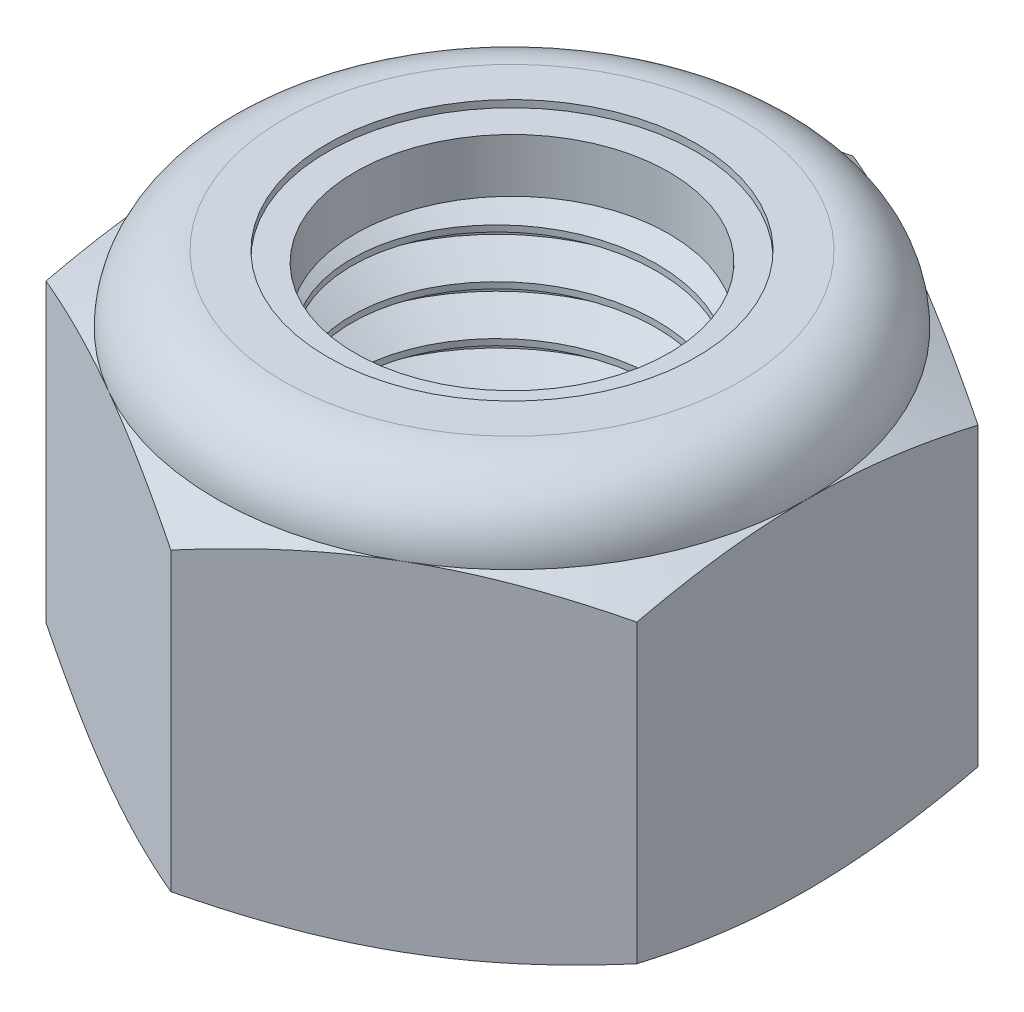
SolidWorks part; units mm, degrees
note: '?' marks a value the reader was unsure of.
ref_plane "Front" through (0, 0, 0) normal (0, 0, 1) x (1, 0, 0)
ref_plane "Top" through (0, 0, 0) normal (0, 1, 0) x (1, 0, 0)
ref_plane "Right" through (0, 0, 0) normal (1, 0, 0) x (0, 0, -1)
sketch "Sketch8" plane through (0, 0, 0) normal (1, 0, 0) x (0, 0, -1)
  line L0 (0, 0) -> (0, 8.7312) construction
  line L1 (6.35, 0) -> (-6.35, 0) construction
  line L2 (-3.9688, 8.7312) -> (3.9688, 8.7312) construction
  line L3 (3.9688, 8.7312) -> (3.9688, 7.6729) construction
sketch "Sketch1" plane through (0, 0, 0) normal (0, 1, 0) x (1, 0, 0)
  line L1 (0, 7.3323) -> (-6.35, 3.6662)
  line L2 (-6.35, 3.6662) -> (-6.35, -3.6662)
  line L3 (-6.35, -3.6662) -> (0, -7.3323)
  line L4 (0, -7.3323) -> (6.35, -3.6662)
  line L5 (6.35, -3.6662) -> (6.35, 3.6662)
  line L6 (6.35, 3.6662) -> (0, 7.3323)
  circle A0 centre (0, 0) radius 6.35 construction
  circle A1 centre (0, 0) radius 3.9688
extrude "Extrude1" add sketch "Sketch1" along normal up to vertex (8.7312 mm away) up to point (0, 8.7312, 0)
sketch "Sketch5" plane through (0, 0, 0) normal (1, 0, 0) x (0, 0, -1)
  line L0 (0, 0) -> (6.35, 0)
  line L1 (6.35, 0) -> (7.3323, 0.4581)
  line L2 (7.3323, 0.4581) -> (7.3323, 6.818)
  line L3 (7.3323, 6.818) -> (6.35, 7.276)
  line L4 (4.8948, 8.7312) -> (4.8948, 10.0012)
  line L5 (4.8948, 10.0012) -> (8.6023, 10.0012)
  line L6 (8.6023, 10.0012) -> (8.6023, -1.27)
  line L7 (8.6023, -1.27) -> (0, -1.27)
  line L8 (0, -1.27) -> (0, 0)
  line L9 (6.35, 7.276) -> (6.35, 0) construction
  line L12 (7.3323, 8.7312) -> (7.3323, 0) construction
  line L13 (7.3323, 4.3656) -> (8.6023, 4.3656) construction
  line L15 (0, 0) -> (0, 10.0012) construction
  line L18 (6.35, 0) -> (-6.35, 0) construction
  line L19 (3.6662, 8.7312) -> (7.3323, 8.7312) construction
  line L20 (0, 10.0012) -> (4.8948, 10.0012) construction
  line L21 (3.6662, 0) -> (7.3323, 0) construction
  arc A0 (6.35, 7.276) -> (4.8948, 8.7312) centre (4.8948, 7.276) ccw
  dimension "D1" = 25
  dimension "D2" = 1.27
  dimension "D4" = 1.4552
revolve "Cut-Revolve3" cut sketch "Sketch5" angle 360 about L15
sketch "Sketch4" plane through (0, 0, 0) normal (1, 0, 0) x (0, 0, -1)
  line L0 (0, 7.276) -> (4.3656, 7.276)
  line L1 (4.3656, 7.276) -> (0, 5.2403)
  line L3 (0, 2.0357) -> (4.3656, 0)
  line L4 (4.3656, 0) -> (0, 0)
  line L5 (0, 0) -> (0, 7.276) construction
  line L10 (0, 0) -> (0, 8.7312) construction
  line L11 (0, 2.0357) -> (0, 0)
  line L12 (0, 7.276) -> (0, 5.2403)
  line L13 (5.4993, 7.276) -> (0, 7.276) construction
  dimension "D1" = 25
  dimension "D2" = 8.7312
sketch "Sketch6" plane through (0, 0, 0) normal (1, 0, 0) x (0, 0, -1)
  line L0 (0, 7.276) -> (6.1976, 7.276)
  line L1 (4.8948, 8.5788) -> (2.4474, 8.5788)
  line L2 (0, 10.0012) -> (0, 7.276)
  line L3 (2.4474, 10.0012) -> (0, 10.0012)
  line L4 (0, 10.0012) -> (4.8948, 10.0012) construction
  line L5 (0, 0) -> (0, 10.0012) construction
  line L6 (0, 10.0012) -> (0, 0) construction
  line L7 (2.4474, 8.5788) -> (2.4474, 10.0012)
  line L8 (4.8948, 8.7312) -> (4.8948, 8.5788) construction
  line L9 (2.4474, 8.5788) -> (0, 8.5788) construction
  line L10 (0, 8.5788) -> (0, 5.2403) construction
  arc A0 (6.1976, 7.276) -> (4.8948, 8.5788) centre (4.8948, 7.276) ccw
  arc A1 (6.35, 7.276) -> (4.8948, 8.7312) centre (4.8948, 7.276) ccw construction
  dimension "D1" = 0.1524
revolve "Cut-Revolve4" cut sketch "Sketch6" angle 360 about L6
revolve "Cut-Revolve2" cut sketch "Sketch4" angle 360 about L5
sketch "Sketch7" plane through (0, 0, 0) normal (1, 0, 0) x (0, 0, -1)
  line L0 (3.3734, 7.3522) -> (6.119, 7.3522)
  line L1 (4.8948, 8.5026) -> (3.3734, 8.5026)
  line L2 (3.3734, 8.5026) -> (3.3734, 7.3522)
  line L3 (3.3734, 7.3522) -> (0, 7.3522) construction
  line L4 (0, 7.3522) -> (0, 8.5026) construction
  line L5 (0, 8.5026) -> (3.3734, 8.5026) construction
  line L6 (3.3734, 7.3522) -> (3.3734, 7.276) construction
  line L7 (0, 7.276) -> (6.1976, 7.276) construction
  line L8 (4.8948, 8.5026) -> (4.8948, 8.5788) construction
  arc A0 (6.119, 7.3522) -> (4.8948, 8.5026) centre (4.8948, 7.276) ccw
  arc A2 (6.1976, 7.276) -> (4.8948, 8.5788) centre (4.8948, 7.276) ccw construction
  dimension "D1" = 0.0762
  dimension "D2" = 6.7469
revolve "Revolve2" add sketch "Sketch7" angle 360 about L4
sketch "Sketch2" plane through (0, 0, 0) normal (1, 0, 0) x (0, 0, -1)
  line L0 (-3.9688, 0) -> (-3.9688, 7.276) construction
  line L1 (0, 0) -> (3.9688, 0)
  line L2 (0, 0) -> (0, 7.276)
  line L3 (0, 7.276) -> (3.9688, 7.276)
  line L4 (3.9688, 0) -> (3.9688, 7.276)
  line L6 (5.4993, 7.276) -> (6.35, 7.276) construction
  line L7 (0, -3.9688) -> (0, 0) construction
revolve "Revolve1" add sketch "Sketch2" angle 360 about L7
sketch "Sketch9" plane through (0, 0, 0) normal (1, 0, 0) x (0, 0, -1)
  line L0 (4.0833, 8.2682) -> (4.0833, 7.2099) construction
  line L1 (4.0833, 7.2099) -> (3.1668, 7.7391) construction
  line L2 (3.1668, 7.7391) -> (4.0833, 8.2682) construction
  line L3 (3.2813, 7.8052) -> (3.2813, 7.6729) construction
  line L4 (3.9688, 8.2021) -> (3.9688, 7.276) construction
  line L5 (3.1668, 7.7391) -> (3.2813, 7.7391) construction
  line L6 (3.9688, 7.7391) -> (4.0833, 7.7391) construction
  line L7 (4.026, 7.7391) -> (4.026, 8.2352) construction
  line L8 (4.0833, 7.2099) -> (4.026, 8.2352)
  line L9 (4.026, 8.2352) -> (3.2813, 7.8052)
  line L10 (3.2813, 7.8052) -> (3.2813, 7.6729)
  line L11 (3.2813, 7.6729) -> (4.0833, 7.2099)
  dimension "D1" = 1.0583
  dimension "D2" = 0.1323
sketch "Sketch10" plane through (0, 7.276, 0) normal (0, 1, 0) x (1, 0, 0)
  circle A1 centre (0, 0) radius 3.9688
  circle A2 centre (0, 0) radius 3.9688
  dimension "D1" = 0
curve "Helix/Spiral1" pitch 1.0583 height 9.7896 turns 9.25
sweep "Cut-Sweep1" cut profiles "Sketch9" path "Helix/Spiral1" align with end faces yes
sketch "Sketch11" plane through (0, 0, 0) normal (1, 0, 0) x (0, 0, -1)
  line L0 (0, 0) -> (0, 8.7312) construction
  line L1 (6.35, 0) -> (-6.35, 0) construction
  line L4 (0, 8.7312) -> (0, 0) construction
  line L5 (0, 4.3656) -> (3.9688, 4.3656) construction
  line L6 (0, 0) -> (4.3656, 0)
  line L7 (0, 2.0357) -> (0, 0)
  line L8 (4.3656, 0) -> (0, 2.0357)
  dimension "D1" = 8.7312
  dimension "D2" = 25
revolve "Revolve3" add sketch "Sketch11" angle 360 about L4
sketch "Sketch12" plane through (0, 0, 0) normal (1, 0, 0) x (0, 0, -1)
  line L0 (4.3656, 7.276) -> (0, 7.276)
  line L1 (0, 7.276) -> (0, 0)
  line L2 (0, 0) -> (4.3656, 0)
  line L3 (6.35, 0) -> (-6.35, 0) construction
  line L4 (4.3656, 0) -> (4.3656, 7.276)
  line L5 (-4.3656, 0) -> (4.3656, 0) construction
revolve "Revolve4" add sketch "Sketch12" angle 360 about L0
combine bodies "Combine1" operation type subtract main body 136 bodies to subtract 133
ref_plane "Contact Plane 1" through (0, 0, 0) normal (0, -1, 0) x (1, 0, 0)
ref_axis "Center Axis 1" through (0, -2.1015, 0) along (0, 1, 0)?
equation "\"D4@Sketch5\"=\"Height@Sketch8\"/6"
equation "\"D1@Sketch9\"=\"Thread Pitch@Sketch8\""
equation "\"D2@Sketch9\"=\"Thread Pitch@Sketch8\"/8"
equation "\"D4@Helix/Spiral1\"=\"Thread Pitch@Sketch8\""
equation "\"D3@Helix/Spiral1\"=\"Thread Pitch@Sketch8\"+\"Height@Sketch8\""
equation "\"D2@Sketch4\"=\"Thread Dia@Sketch8\"*1.1"
equation "\"D1@Sketch11\"=\"Thread Dia@Sketch8\"*1.1"
equation "\"D2@Sketch7\"=\"Thread Dia@Sketch8\"*.85"
